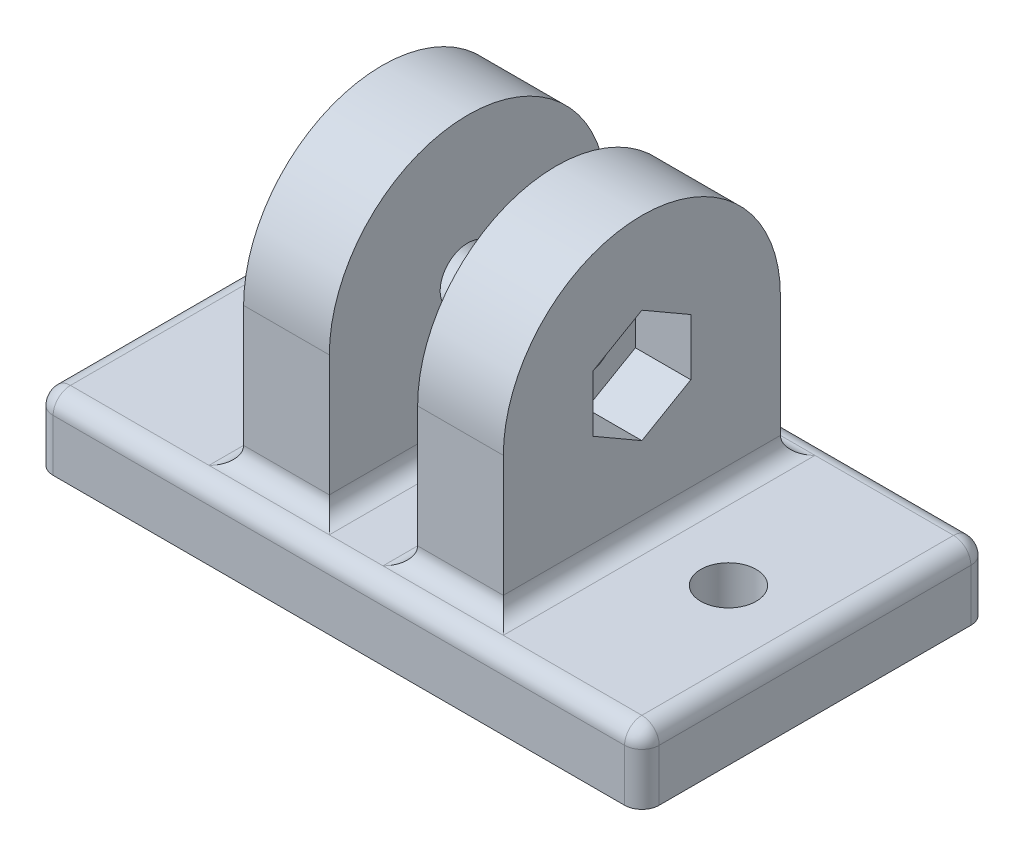
SolidWorks part; units mm, degrees
ref_plane "Front Plane" through (0, 0, 0) normal (1, 0, 0) x (0, 1, 0)
ref_plane "Top Plane" through (0, 0, 0) normal (0, 0, 1) x (0, 1, 0)
ref_plane "Right Plane" through (0, 0, 0) normal (0, 1, 0) x (-1, 0, 0)
sketch "Sketch1" plane through (0, 0, 0) normal (1, 0, 0) x (0, 1, 0)
  line L1 (-10, 10) -> (10, 10)
  line L2 (-10, 10) -> (-10, -10)
  line L3 (-10, -10) -> (10, -10)
  line L4 (10, 10) -> (10, -10)
  line L5 (-10, 10) -> (10, -10) construction
  line L6 (-10, -10) -> (10, 10) construction
  point P0 (0, 0)
  dimension "D1" = 20
  dimension "D2" = 20
extrude "Boss-Extrude1" add sketch "Sketch1" along normal blind 15
ref_plane "Plane1" through (7.5, 0, 0) normal (-1, 0, 0) x (0, 0, 1)
sketch "Sketch2" plane through (7.5, 0, 0) normal (-1, 0, 0) x (0, 0, 1)
  line L1 (-10, -10) -> (-10, 10) construction
  line L2 (-10, 0) -> (-10, 10)
  line L3 (-10, 10) -> (10, 10) construction
  line L5 (10, 10) -> (10, 0)
  line L6 (10, 10) -> (10, -10) construction
  line L8 (-8, 2) -> (-8, -6)
  line L9 (-8, -6) -> (-10, -6)
  line L10 (-10, -6) -> (-10, 0)
  line L11 (-10, 10) -> (10, 10)
  line L12 (0, 0) -> (0, 14.4574) construction
  line L13 (10, -6) -> (10, 0)
  line L14 (8, -6) -> (10, -6)
  line L15 (8, 2) -> (8, -6)
  line L16 (10, 0) -> (10, 10)
  arc A0 (-8, 2) -> (8, 2) centre (0, 2) cw
  point P20 (0, 10)
  dimension "D1" = 8
  dimension "D2" = 2
  dimension "D3" = 8
extrude "Cut-Extrude1" cut sketch "Sketch2" against normal through all both and the other way through all contours L8 A0 L11 L2 L10 L9 | L11 A0 L15 L14 L13 L5 region at (7.5, 3.8658, 8.1631) region at (7.5, 3.8658, -8.1631)
sketch "Sketch3" plane through (7.5, 0, 0) normal (-1, 0, 0) x (0, 0, 1)
  line L0 (-10, -6) -> (10, -6)
  line L1 (-10, -10) -> (-10, -6) construction
  line L2 (10, -6) -> (10, -10) construction
  line L3 (10, -6) -> (10, 10)
  line L4 (10, 10) -> (-10, 10)
  line L5 (-10, 10) -> (-10, -6)
  arc A0 (8, 2) -> (-8, 2) centre (0, 2) ccw construction
  dimension "D1" = 16
extrude "Cut-Extrude2" cut sketch "Sketch3" against normal mid plane 5.1
sketch "Sketch4" plane through (7.5, 0, 0) normal (-1, 0, 0) x (0, 0, 1)
  circle A0 centre (0, 2) radius 1.6
  dimension "D1" = 3.2
extrude "Cut-Extrude3" cut sketch "Sketch4" against normal through all both and the other way through all
sketch "Sketch5" plane through (7.5, 0, 0) normal (-1, 0, 0) x (0, 0, 1)
  line L1 (-10, -10) -> (10, -10)
  line L2 (-10, -10) -> (-10, -6)
  line L3 (-10, -6) -> (10, -6)
  line L4 (10, -10) -> (10, -6)
extrude "Boss-Extrude2" add sketch "Sketch5" along normal mid plane 35
sketch "Sketch6" plane through (0, -6, 0) normal (0, 1, 0) x (1, 0, 0)
  line L4 (25, -10) -> (25, 10) construction
  line L6 (7.5, 11) -> (7.5, -11) construction
  circle A0 centre (20, 0) radius 1.6
  circle A1 centre (-5, 0) radius 1.6
  dimension "D1" = 3.2
  dimension "D2" = 5
extrude "Cut-Extrude4" cut sketch "Sketch6" against normal through all both and the other way through all
fillet "Fillet4" radius 1 16 edges at (12.525, -6, -8) (10.05, -6, 0) (12.525, -6, 8) (15, -6, 0) (0, -6, 0) (2.475, -6, 8) (4.95, -6, 0) (2.475, -6, -8) (-10, -6, 0) (7.5, -6, -10) (25, -6, 0) (7.5, -6, 10) (-10, -8, -10) (-10, -8, 10) (25, -8, 10) (25, -8, -10)
sketch "Sketch7" plane through (15, 0, 0) normal (1, 0, 0) x (0, 1, 0)
  line L1 (3.631, -2.825) -> (5.262, 0)
  line L2 (5.262, 0) -> (3.631, 2.825)
  line L3 (3.631, 2.825) -> (0.369, 2.825)
  line L4 (0.369, 2.825) -> (-1.262, 0)
  line L5 (-1.262, 0) -> (0.369, -2.825)
  line L6 (0.369, -2.825) -> (3.631, -2.825)
  circle A0 centre (2, 0) radius 2.825 construction
  dimension "D1" = 5.65
extrude "Cut-Extrude5" cut sketch "Sketch7" against normal blind 3.2 contours L3 L4 L5 L6 L1 L2
